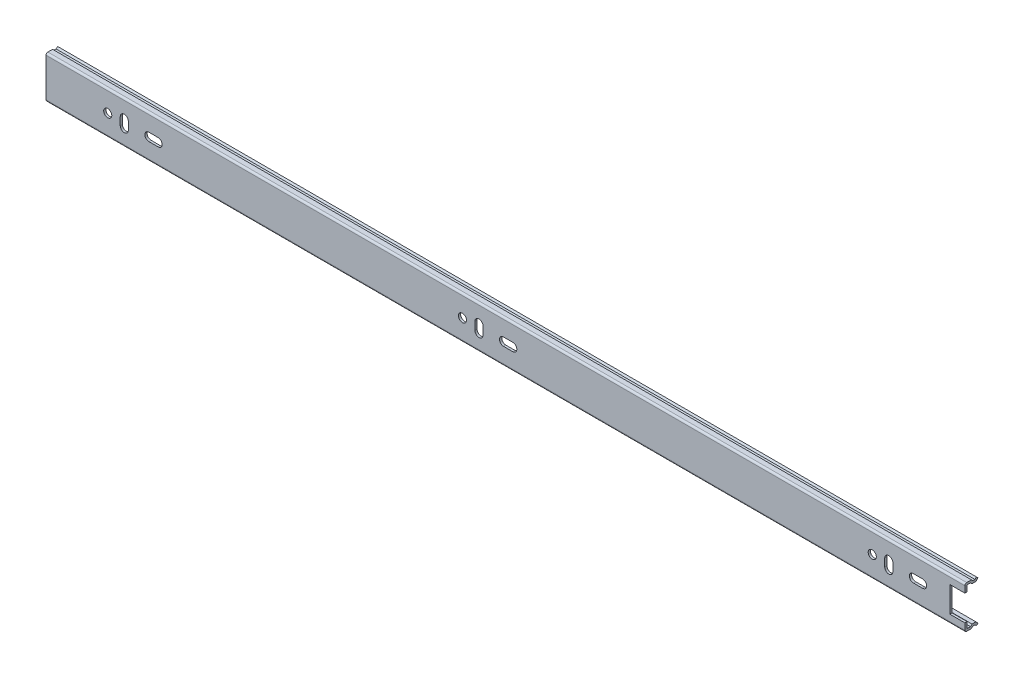
SolidWorks part; units mm, degrees
ref_plane "Спереди" through (0, 0, 0) normal (0, 0, 1) x (1, 0, 0)
ref_plane "Сверху" through (0, 0, 0) normal (0, 1, 0) x (1, 0, 0)
ref_plane "Справа" through (0, 0, 0) normal (1, 0, 0) x (0, 0, -1)
sketch "Эскиз1" plane through (0, 0, 0) normal (1, 0, 0) x (0, 0, -1)
  line L0 (0, 10.5) -> (0, -10.5)
  line L1 (-12.4481, 0) -> (26.4522, 0) construction
  line L2 (3.5733, 11.5) -> (1, 11.5)
  line L3 (4.3714, 10.7019) -> (3.5733, 11.5)
  line L4 (5.5019, 10.7019) -> (4.3714, 10.7019)
  line L5 (6.3, -11.5) -> (5.5019, -10.7019)
  line L6 (5.5019, -10.7019) -> (4.3714, -10.7019)
  line L7 (4.3714, -10.7019) -> (3.5733, -11.5)
  line L8 (3.5733, -11.5) -> (1, -11.5)
  line L9 (6.3, 11.5) -> (5.5019, 10.7019)
  arc A0 (0, 10.5) -> (1, 11.5) centre (1, 10.5) cw
  arc A2 (0, -10.5) -> (1, -11.5) centre (1, -10.5) ccw
  point P0 (0, -11.5)
  point P1 (0, 11.5)
  point P12 (0, 0)
  point P20 (0, 0)
extrude "Вытянуть-Тонкостенный3" add sketch "Эскиз1" along normal blind 500 thin thin type one direction wall 1.2
sketch "Эскиз2" plane through (0, 0, 0) normal (0, 0, 1) x (1, 0, 0)
  line L0 (500, -10.5) -> (500, 10.5) construction
  line L1 (500, 7) -> (491.8, 7)
  line L2 (500, 7) -> (500, -7)
  line L3 (500, -7) -> (491.8, -7)
  line L4 (491.8, 7) -> (491.8, -7)
  line L5 (472, 2.2) -> (477, 2.2)
  line L6 (472, -2.2) -> (477, -2.2)
  line L7 (456.4, 1.7796) -> (456.4, -2.5)
  line L8 (460.8, -2.5) -> (460.8, 1.7796)
  line L9 (233.4, 1.7796) -> (233.4, -2.5)
  line L10 (237.8, -2.5) -> (237.8, 1.7796)
  line L11 (249, -2.2) -> (254, -2.2)
  line L12 (249, 2.2) -> (254, 2.2)
  line L13 (44.8, -2.5) -> (44.8, 1.7796)
  line L14 (40.4, 1.7796) -> (40.4, -2.5)
  line L15 (56, 2.2) -> (61, 2.2)
  line L16 (56, -2.2) -> (61, -2.2)
  circle A0 centre (449.6, 0) radius 2.2
  arc A1 (472, 2.2) -> (472, -2.2) centre (472, 0) ccw
  arc A2 (477, 2.2) -> (477, -2.2) centre (477, 0) cw
  arc A3 (456.4, -2.5) -> (460.8, -2.5) centre (458.6, -2.5) ccw
  arc A4 (460.8, 1.7796) -> (456.4, 1.7796) centre (458.6, 1.7796) ccw
  arc A5 (233.4, -2.5) -> (237.8, -2.5) centre (235.6, -2.5) ccw
  circle A6 centre (226.6, 0) radius 2.2
  arc A7 (237.8, 1.7796) -> (233.4, 1.7796) centre (235.6, 1.7796) ccw
  arc A8 (249, 2.2) -> (249, -2.2) centre (249, 0) ccw
  arc A9 (254, 2.2) -> (254, -2.2) centre (254, 0) cw
  arc A10 (40.4, -2.5) -> (44.8, -2.5) centre (42.6, -2.5) ccw
  arc A11 (44.8, 1.7796) -> (40.4, 1.7796) centre (42.6, 1.7796) ccw
  circle A12 centre (33.6, 0) radius 2.2
  arc A13 (61, 2.2) -> (61, -2.2) centre (61, 0) cw
  arc A14 (56, 2.2) -> (56, -2.2) centre (56, 0) ccw
extrude "Вырез-Вытянуть1" cut sketch "Эскиз2" against normal through all
